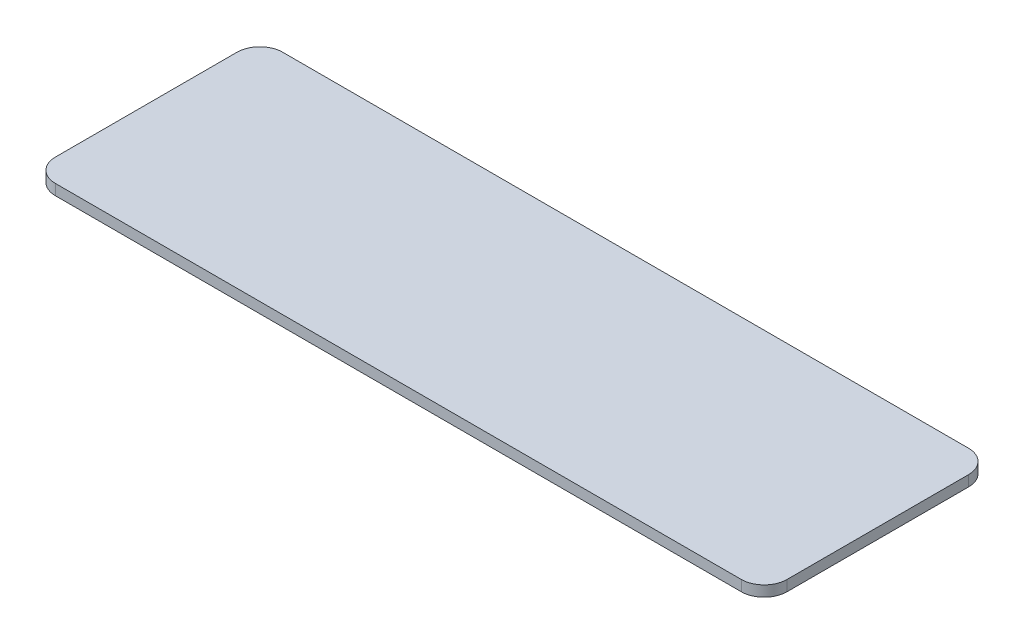
SolidWorks part; units mm, degrees
material "ABS PC"
ref_plane "Front Plane" through (0, 0, 0) normal (0, 0, 1) x (1, 0, 0)
ref_plane "Top Plane" through (0, 0, 0) normal (0, 1, 0) x (1, 0, 0)
ref_plane "Right Plane" through (0, 0, 0) normal (1, 0, 0) x (0, 0, -1)
ref_axis "Axis1" through (0, 0, -88.99) along (0, 0, 1)
ref_axis "Axis2" through (0, -55, 0) along (0, 1, 0)
ref_axis "Axis3" through (-88.99, 0, 0) along (1, 0, 0)
sketch "Sketch1" plane through (0, 0, 0) normal (0, 1, 0) x (1, 0, 0)
  line L1 (51, -16.9) -> (-51, -16.9)
  line L2 (54.4, -13.5) -> (54.4, 13.5)
  line L3 (51, 16.9) -> (-51, 16.9)
  line L4 (-54.4, -13.5) -> (-54.4, 13.5)
  line L5 (54.4, -16.9) -> (-54.4, 16.9) construction
  line L6 (54.4, 16.9) -> (-54.4, -16.9) construction
  arc A0 (54.4, 13.5) -> (51, 16.9) centre (51, 13.5) ccw
  arc A1 (51, -16.9) -> (54.4, -13.5) centre (51, -13.5) ccw
  arc A2 (-51, -16.9) -> (-54.4, -13.5) centre (-51, -13.5) cw
  arc A3 (-51, 16.9) -> (-54.4, 13.5) centre (-51, 13.5) ccw
  point P0 (0, 0)
  dimension "D1" = 3.4
  dimension "D2" = 33.8
  dimension "D3" = 108.8
extrude "Boss-Extrude1" add sketch "Sketch1" along normal blind 1.5875
